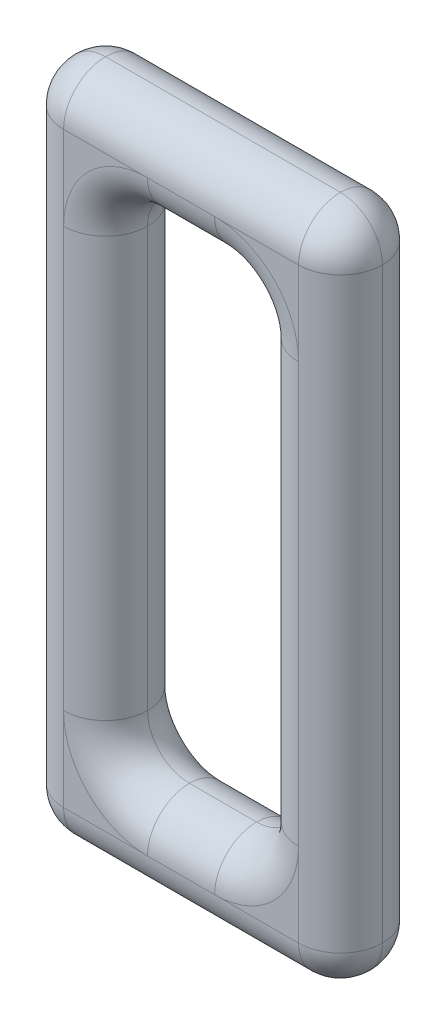
SolidWorks part; units mm, degrees
ref_plane "Front Plane" through (0, 0, 0) normal (0, 0, 1) x (1, 0, 0)
ref_plane "Top Plane" through (0, 0, 0) normal (0, 1, 0) x (1, 0, 0)
ref_plane "Right Plane" through (0, 0, 0) normal (1, 0, 0) x (0, 0, -1)
sketch "Sketch1" plane through (0, 0, 0) normal (0, 0, 1) x (1, 0, 0)
  line L0 (0, 0) -> (0, 25) construction
  line L1 (-95, 25) -> (95, 25)
  line L2 (-95, 25) -> (-95, -375)
  line L3 (-95, -375) -> (95, -375)
  line L4 (95, 25) -> (95, -375)
  line L5 (-45, -25) -> (45, -25)
  line L6 (-45, -25) -> (-45, -325)
  line L7 (-45, -325) -> (45, -325)
  line L8 (45, -25) -> (45, -325)
  dimension "D1" = 25
  dimension "D2" = 50
  dimension "D3" = 400
  dimension "D4" = 190
  dimension "D5" = 50
  dimension "D6" = 50
  dimension "D7" = 50
extrude "Boss-Extrude1" add sketch "Sketch1" along normal mid plane 50
fillet "Fillet1" radius 25 16 edges at (-45, -175, -25) (0, -25, -25) (0, -325, -25) (45, -175, 25) (45, -175, -25) (0, -375, 25) (95, -175, 25) (95, -175, -25) (0, -375, -25) (-95, -175, -25) (0, 25, -25) (0, -325, 25) (-45, -175, 25) (-95, -175, 25) (0, -25, 25) (0, 25, 25)
